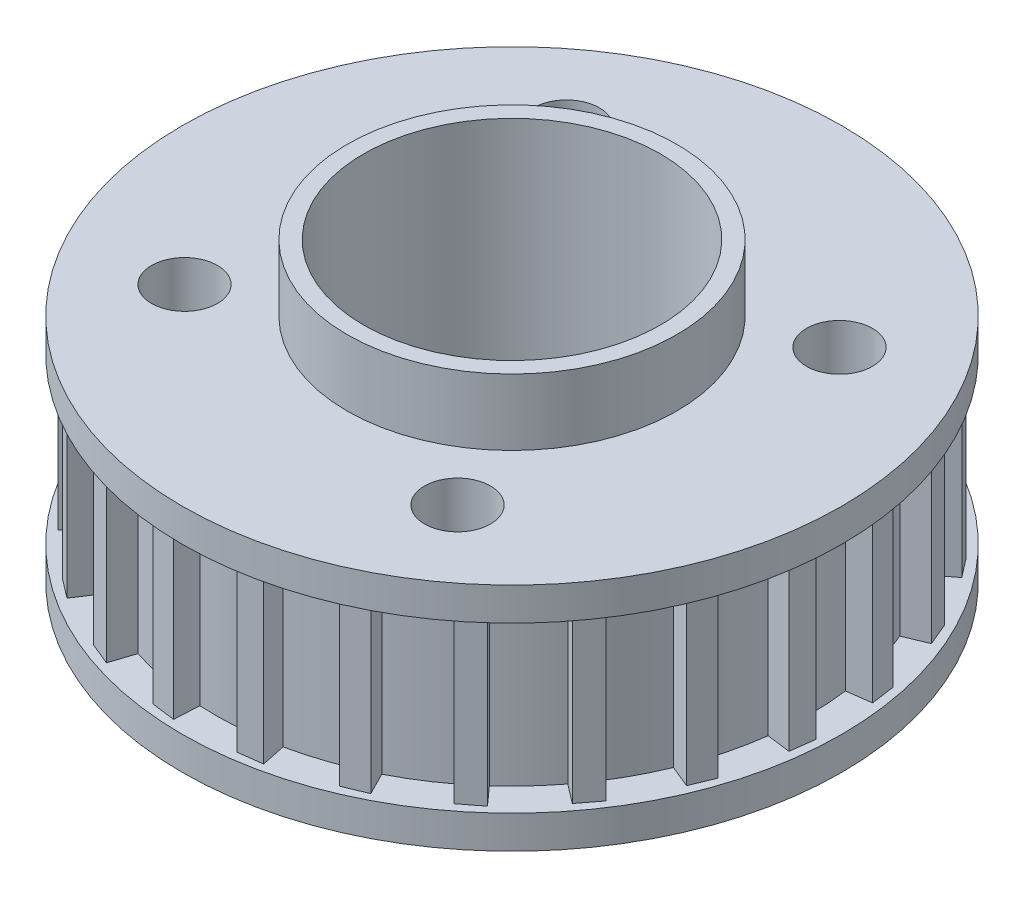
SolidWorks part; units mm, degrees
ref_plane "Front Plane" through (0, 0, 0) normal (0, 0, 1) x (1, 0, 0)
ref_plane "Top Plane" through (0, 0, 0) normal (0, 1, 0) x (1, 0, 0)
ref_plane "Right Plane" through (0, 0, 0) normal (1, 0, 0) x (0, 0, -1)
sketch "Sketch1" plane through (0, 0, 0) normal (0, 1, 0) x (1, 0, 0)
  circle A0 centre (0, 0) radius 31.75
  circle A1 centre (0, 0) radius 14.2875
  dimension "D1" = 28.575
  dimension "D2" = 63.5
extrude "Boss-Extrude1" add sketch "Sketch1" along normal blind 3.175
sketch "Sketch2" plane through (0, 3.175, 0) normal (0, 1, 0) x (1, 0, 0)
  circle A0 centre (0, 0) radius 14.2875
  circle A1 centre (0, 0) radius 15.875
  dimension "D1" = 31.75
extrude "Boss-Extrude2" add sketch "Sketch2" along normal blind 25.4
sketch "Sketch3" plane through (0, 3.175, 0) normal (0, 1, 0) x (1, 0, 0)
  circle A0 centre (-18.3907, -13.1458) radius 3.175
  circle A1 centre (-13.1458, 18.3907) radius 3.175
  circle A2 centre (18.3907, 13.1458) radius 3.175
  circle A3 centre (13.1458, -18.3907) radius 3.175
  point P12 (0, 0)
  dimension "D2" = 6.35
  dimension "D1" = 22.606
  dimension "D3" = 4
extrude "Cut-Extrude1" cut sketch "Sketch3" against normal blind 25.4
sketch "Sketch4" plane through (0, 3.175, 0) normal (0, 1, 0) x (1, 0, 0)
  line L0 (-10.8637, -26.4128) -> (-11.7467, -28.5597)
  line L1 (-11.7467, -28.5597) -> (-9.6165, -29.4358)
  line L2 (-9.6165, -29.4358) -> (-8.869, -27.1477)
  line L3 (-17.3296, -22.7011) -> (-18.7382, -24.5463)
  line L4 (-18.7382, -24.5463) -> (-16.9074, -25.9439)
  line L5 (-16.9074, -25.9439) -> (-15.5931, -23.9272)
  line L6 (-22.6146, -17.4423) -> (-24.4528, -18.8601)
  line L7 (-24.4528, -18.8601) -> (-23.0461, -20.6839)
  line L8 (-23.0461, -20.6839) -> (-21.2546, -19.0761)
  line L9 (-26.3584, -10.9949) -> (-28.5009, -11.8886)
  line L10 (-28.5009, -11.8886) -> (-27.6142, -14.0144)
  line L11 (-27.6142, -14.0144) -> (-25.4676, -12.925)
  line L12 (-28.306, -3.7982) -> (-30.6067, -4.1069)
  line L13 (-30.6067, -4.1069) -> (-30.3004, -6.3898)
  line L14 (-30.3004, -6.3898) -> (-27.9451, -5.8931)
  line L15 (-28.3245, 3.6573) -> (-30.6268, 3.9546)
  line L16 (-30.6268, 3.9546) -> (-30.9218, 1.6703)
  line L17 (-30.9218, 1.6703) -> (-28.5181, 1.5405)
  line L18 (-26.4128, 10.8637) -> (-28.5597, 11.7467)
  line L19 (-28.5597, 11.7467) -> (-29.4358, 9.6165)
  line L20 (-29.4358, 9.6165) -> (-27.1477, 8.869)
  line L21 (-22.7011, 17.3296) -> (-24.5463, 18.7382)
  line L22 (-24.5463, 18.7382) -> (-25.9439, 16.9074)
  line L23 (-25.9439, 16.9074) -> (-23.9272, 15.5931)
  line L24 (-17.4423, 22.6146) -> (-18.8601, 24.4528)
  line L25 (-18.8601, 24.4528) -> (-20.6839, 23.0461)
  line L26 (-20.6839, 23.0461) -> (-19.0761, 21.2546)
  line L27 (-10.9949, 26.3584) -> (-11.8886, 28.5009)
  line L28 (-11.8886, 28.5009) -> (-14.0144, 27.6142)
  line L29 (-14.0144, 27.6142) -> (-12.925, 25.4676)
  line L30 (-3.7982, 28.306) -> (-4.1069, 30.6067)
  line L31 (-4.1069, 30.6067) -> (-6.3898, 30.3004)
  line L32 (-6.3898, 30.3004) -> (-5.8931, 27.9451)
  line L33 (3.6573, 28.3245) -> (3.9546, 30.6268)
  line L34 (3.9546, 30.6268) -> (1.6703, 30.9218)
  line L35 (1.6703, 30.9218) -> (1.5405, 28.5181)
  line L36 (10.8637, 26.4128) -> (11.7467, 28.5597)
  line L37 (11.7467, 28.5597) -> (9.6165, 29.4358)
  line L38 (9.6165, 29.4358) -> (8.869, 27.1477)
  line L39 (17.3296, 22.7011) -> (18.7382, 24.5463)
  line L40 (18.7382, 24.5463) -> (16.9074, 25.9439)
  line L41 (16.9074, 25.9439) -> (15.5931, 23.9272)
  line L42 (22.6146, 17.4423) -> (24.4528, 18.8601)
  line L43 (24.4528, 18.8601) -> (23.0461, 20.6839)
  line L44 (23.0461, 20.6839) -> (21.2546, 19.0761)
  line L45 (26.3584, 10.9949) -> (28.5009, 11.8886)
  line L46 (28.5009, 11.8886) -> (27.6142, 14.0144)
  line L47 (27.6142, 14.0144) -> (25.4676, 12.925)
  line L48 (28.306, 3.7982) -> (30.6067, 4.1069)
  line L49 (30.6067, 4.1069) -> (30.3004, 6.3898)
  line L50 (30.3004, 6.3898) -> (27.9451, 5.8931)
  line L51 (28.3245, -3.6573) -> (30.6268, -3.9546)
  line L52 (30.6268, -3.9546) -> (30.9218, -1.6703)
  line L53 (30.9218, -1.6703) -> (28.5181, -1.5405)
  line L54 (26.4128, -10.8637) -> (28.5597, -11.7467)
  line L55 (28.5597, -11.7467) -> (29.4358, -9.6165)
  line L56 (29.4358, -9.6165) -> (27.1477, -8.869)
  line L57 (22.7011, -17.3296) -> (24.5463, -18.7382)
  line L58 (24.5463, -18.7382) -> (25.9439, -16.9074)
  line L59 (25.9439, -16.9074) -> (23.9272, -15.5931)
  line L60 (17.4423, -22.6146) -> (18.8601, -24.4528)
  line L61 (18.8601, -24.4528) -> (20.6839, -23.0461)
  line L62 (20.6839, -23.0461) -> (19.0761, -21.2546)
  line L63 (10.9949, -26.3584) -> (11.8886, -28.5009)
  line L64 (11.8886, -28.5009) -> (14.0144, -27.6142)
  line L65 (14.0144, -27.6142) -> (12.925, -25.4676)
  line L66 (3.7982, -28.306) -> (4.1069, -30.6067)
  line L67 (4.1069, -30.6067) -> (6.3898, -30.3004)
  line L68 (6.3898, -30.3004) -> (5.8931, -27.9451)
  line L69 (-3.6573, -28.3245) -> (-3.9546, -30.6268)
  line L70 (-3.9546, -30.6268) -> (-1.6703, -30.9218)
  line L71 (-1.6703, -30.9218) -> (-1.5405, -28.5181)
  circle A0 centre (0, 0) radius 15.875
  circle A1 centre (0, 0) radius 28.5597
  circle A2 centre (-18.3907, -13.1458) radius 3.175
  circle A3 centre (-13.1458, 18.3907) radius 3.175
  circle A4 centre (18.3907, 13.1458) radius 3.175
  circle A5 centre (13.1458, -18.3907) radius 3.175
  point P102 (0, 0)
  circle M1 centre (13.1458, -18.3907) radius 3.175
  dimension "D1" = 24
extrude "Boss-Extrude3" add sketch "Sketch4" along normal blind 15.8496 contours A1 M1 region at (-12.9108, 3.175, 24.5658)
extrude "Boss-Extrude4" add sketch "Sketch4<9>" along normal blind 15.875 contours A1 L54 L55 L56 | A1 L51 L52 L53 | A1 L48 L49 L50 | A1 L45 L46 L47 | A1 L42 L43 L44 | A1 L39 L40 L41 | A1 L36 L37 L38 | A1 L33 L34 L35 | A1 L30 L31 L32 | A1 L27 L28 L29 | A1 L24 L25 L26 | A1 L21 L22 L23 | A1 L18 L19 L20 | A1 L15 L16 L17 | A1 L12 L13 L14 | A1 L9 L10 L11 | A1 L6 L7 L8 | A1 L3 L4 L5 | A1 L0 L1 L2 | A1 L69 L70 L71 | A1 L66 L67 L68 | A1 L63 L64 L65 | A1 L57 L58 L59 | A1 L60 L61 L62 region at (-10.2755, 3.175, 27.9121) region at (-17.1496, 3.175, 24.3015) region at (-2.7012, 3.175, 29.6205) region at (-22.8549, 3.175, 19.0348) region at (5.0571, 3.175, 29.3103) region at (-27.0027, 3.175, 12.4709) region at (12.4709, 3.175, 27.0027) region at (-29.3103, 3.175, 5.0571) region at (19.0348, 3.175, 22.8549) region at (-29.6205, 3.175, -2.7012) region at (24.3015, 3.175, 17.1496) region at (-27.9121, 3.175, -10.2755) region at (27.9121, 3.175, 10.2755) region at (-24.3015, 3.175, -17.1496) region at (29.6205, 3.175, 2.7012) region at (-19.0348, 3.175, -22.8549) region at (-12.4709, 3.175, -27.0027) region at (29.3103, 3.175, -5.0571) region at (-5.0571, 3.175, -29.3103) region at (27.0027, 3.175, -12.4709) region at (2.7012, 3.175, -29.6205) region at (22.8549, 3.175, -19.0348) region at (10.2755, 3.175, -27.9121) region at (17.1496, 3.175, -24.3015)
sketch "Sketch4<9>" plane through (0, 3.175, 0) normal (0, 1, 0) x (1, 0, 0) same geometry as "Sketch4"
sketch "Sketch5" plane through (0, 19.0246, 0) normal (0, 1, 0) x (1, 0, 0)
  circle A0 centre (0, 0) radius 15.875
  circle A1 centre (0, 0) radius 31.75
  circle A2 centre (13.1458, -18.3907) radius 3.175
  circle A3 centre (-18.3907, -13.1458) radius 3.175
  circle A4 centre (-13.1458, 18.3907) radius 3.175
  circle A5 centre (18.3907, 13.1458) radius 3.175
  dimension "D1" = 63.5
extrude "Boss-Extrude5" add sketch "Sketch5" along normal blind 3.175
